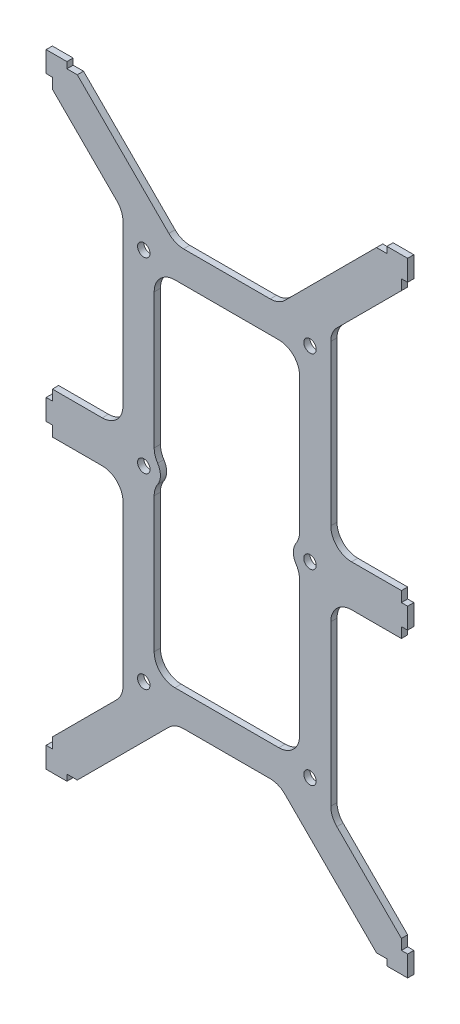
SolidWorks part; units mm, degrees
material "1023 Arkusz stali węglowej (SS)"
ref_plane "Płaszczyzna przednia" through (0, 0, 0) normal (0, 0, 1) x (1, 0, 0)
ref_plane "Płaszczyzna górna" through (0, 0, 0) normal (0, 1, 0) x (1, 0, 0)
ref_plane "Płaszczyzna prawa" through (0, 0, 0) normal (1, 0, 0) x (0, 0, -1)
sketch "Szkic1" plane through (0, 0, 0) normal (0, 0, 1) x (1, 0, 0)
  line L374 (-551.4403, 234.8816) -> (-551.4403, 224.8816)
  line L375 (-551.4403, 224.8816) -> (-548.4403, 224.8816)
  line L376 (-548.4403, 224.8816) -> (-548.4403, 219.8816)
  line L377 (-551.4403, 234.8816) -> (-541.4403, 234.8816)
  line L378 (-541.4403, 234.8816) -> (-541.4403, 231.8816)
  line L379 (-541.4403, 231.8816) -> (-536.4403, 231.8816)
  line L380 (-536.4403, 231.8816) -> (-492.3692, 187.8105)
  line L381 (-514.4403, 181.7395) -> (-514.4403, 104.8816)
  line L382 (-499.4403, 159.8816) -> (-499.4403, 94.8315)
  line L383 (-548.4403, 219.8816) -> (-517.3692, 188.8105)
  line L384 (-551.4403, 89.8816) -> (-548.4403, 89.8816)
  line L385 (-548.4403, 94.8816) -> (-548.4403, 89.8816)
  line L386 (-548.4403, 94.8816) -> (-524.4403, 94.8816)
  line L387 (-551.4403, 89.8816) -> (-551.4403, 84.8816)
  line L388 (-485.2981, 184.8816) -> (-464.4403, 184.8816)
  line L389 (-489.4403, 169.8816) -> (-464.4403, 169.8816)
  line L390 (-377.4403, 234.8816) -> (-377.4403, 224.8816)
  line L391 (-377.4403, 224.8816) -> (-380.4403, 224.8816)
  line L392 (-380.4403, 224.8816) -> (-380.4403, 219.8816)
  line L393 (-377.4403, 234.8816) -> (-387.4403, 234.8816)
  line L394 (-387.4403, 234.8816) -> (-387.4403, 231.8816)
  line L395 (-387.4403, 231.8816) -> (-392.4403, 231.8816)
  line L396 (-392.4403, 231.8816) -> (-436.5113, 187.8105)
  line L397 (-414.4403, 181.7395) -> (-414.4403, 104.8816)
  line L398 (-429.4403, 159.8816) -> (-429.4403, 94.8315)
  line L399 (-380.4403, 219.8816) -> (-411.5113, 188.8105)
  line L400 (-377.4403, 89.8816) -> (-380.4403, 89.8816)
  line L401 (-380.4403, 94.8816) -> (-380.4403, 89.8816)
  line L402 (-380.4403, 94.8816) -> (-404.4403, 94.8816)
  line L403 (-377.4403, 89.8816) -> (-377.4403, 84.8816)
  line L404 (-443.5824, 184.8816) -> (-464.4403, 184.8816)
  line L405 (-439.4403, 169.8816) -> (-464.4403, 169.8816)
  line L406 (-551.4403, -65.1184) -> (-551.4403, -55.1184)
  line L407 (-551.4403, -55.1184) -> (-548.4403, -55.1184)
  line L408 (-548.4403, -55.1184) -> (-548.4403, -50.1184)
  line L409 (-551.4403, -65.1184) -> (-541.4403, -65.1184)
  line L410 (-541.4403, -65.1184) -> (-541.4403, -62.1184)
  line L411 (-541.4403, -62.1184) -> (-536.4403, -62.1184)
  line L412 (-536.4403, -62.1184) -> (-492.3692, -18.0473)
  line L413 (-514.4403, -11.9763) -> (-514.4403, 64.8816)
  line L414 (-499.4403, 9.8816) -> (-499.4403, 74.9317)
  line L415 (-548.4403, -50.1184) -> (-517.3692, -19.0473)
  line L416 (-551.4403, 79.8816) -> (-548.4403, 79.8816)
  line L417 (-548.4403, 74.8816) -> (-548.4403, 79.8816)
  line L418 (-548.4403, 74.8816) -> (-524.4403, 74.8816)
  line L419 (-551.4403, 79.8816) -> (-551.4403, 84.8816)
  line L420 (-485.2981, -15.1184) -> (-464.4403, -15.1184)
  line L421 (-489.4403, -0.1184) -> (-464.4403, -0.1184)
  line L422 (-377.4403, -65.1184) -> (-377.4403, -55.1184)
  line L423 (-377.4403, -55.1184) -> (-380.4403, -55.1184)
  line L424 (-380.4403, -55.1184) -> (-380.4403, -50.1184)
  line L425 (-377.4403, -65.1184) -> (-387.4403, -65.1184)
  line L426 (-387.4403, -65.1184) -> (-387.4403, -62.1184)
  line L427 (-387.4403, -62.1184) -> (-392.4403, -62.1184)
  line L428 (-392.4403, -62.1184) -> (-436.5113, -18.0473)
  line L429 (-414.4403, -11.9763) -> (-414.4403, 64.8816)
  line L430 (-429.4403, 9.8816) -> (-429.4403, 74.9317)
  line L431 (-380.4403, -50.1184) -> (-411.5113, -19.0473)
  line L432 (-377.4403, 79.8816) -> (-380.4403, 79.8816)
  line L433 (-380.4403, 74.8816) -> (-380.4403, 79.8816)
  line L434 (-380.4403, 74.8816) -> (-404.4403, 74.8816)
  line L435 (-377.4403, 79.8816) -> (-377.4403, 84.8816)
  line L436 (-443.5824, -15.1184) -> (-464.4403, -15.1184)
  line L437 (-439.4403, -0.1184) -> (-464.4403, -0.1184)
  arc A162 (-514.4403, 181.7395) -> (-517.3692, 188.8105) centre (-524.4403, 181.7395) ccw
  arc A163 (-489.4403, 169.8816) -> (-499.4403, 159.8816) centre (-489.4403, 159.8816) ccw
  arc A164 (-492.3692, 187.8105) -> (-485.2981, 184.8816) centre (-485.2981, 194.8816) ccw
  arc A165 (-524.4403, 94.8816) -> (-514.4403, 104.8816) centre (-524.4403, 104.8816) ccw
  circle A166 centre (-504.4403, 174.8816) radius 3
  arc A167 (-496.4403, 84.8816) -> (-497.7736, 89.3038) centre (-504.4403, 84.8816) ccw
  arc A168 (-501.4403, 84.8816) -> (-507.4403, 84.8816) centre (-504.4403, 84.8816) ccw
  arc A169 (-499.4403, 94.8315) -> (-497.7736, 89.3038) centre (-489.4403, 94.8315) ccw
  arc A170 (-411.5113, 188.8105) -> (-414.4403, 181.7395) centre (-404.4403, 181.7395) ccw
  arc A171 (-429.4403, 159.8816) -> (-439.4403, 169.8816) centre (-439.4403, 159.8816) ccw
  arc A172 (-443.5824, 184.8816) -> (-436.5113, 187.8105) centre (-443.5824, 194.8816) ccw
  arc A173 (-414.4403, 104.8816) -> (-404.4403, 94.8816) centre (-404.4403, 104.8816) ccw
  circle A174 centre (-424.4403, 174.8816) radius 3
  arc A175 (-431.1069, 89.3038) -> (-432.4403, 84.8816) centre (-424.4403, 84.8816) ccw
  arc A176 (-421.4403, 84.8816) -> (-427.4403, 84.8816) centre (-424.4403, 84.8816) ccw
  arc A177 (-431.1069, 89.3038) -> (-429.4403, 94.8315) centre (-439.4403, 94.8315) ccw
  arc A178 (-517.3692, -19.0473) -> (-514.4403, -11.9763) centre (-524.4403, -11.9763) ccw
  arc A179 (-499.4403, 9.8816) -> (-489.4403, -0.1184) centre (-489.4403, 9.8816) ccw
  arc A180 (-485.2981, -15.1184) -> (-492.3692, -18.0473) centre (-485.2981, -25.1184) ccw
  arc A181 (-514.4403, 64.8816) -> (-524.4403, 74.8816) centre (-524.4403, 64.8816) ccw
  circle A182 centre (-504.4403, -5.1184) radius 3
  arc A183 (-497.7736, 80.4594) -> (-496.4403, 84.8816) centre (-504.4403, 84.8816) ccw
  arc A184 (-507.4403, 84.8816) -> (-501.4403, 84.8816) centre (-504.4403, 84.8816) ccw
  arc A185 (-497.7736, 80.4594) -> (-499.4403, 74.9317) centre (-489.4403, 74.9317) ccw
  arc A186 (-414.4403, -11.9763) -> (-411.5113, -19.0473) centre (-404.4403, -11.9763) ccw
  arc A187 (-439.4403, -0.1184) -> (-429.4403, 9.8816) centre (-439.4403, 9.8816) ccw
  arc A188 (-436.5113, -18.0473) -> (-443.5824, -15.1184) centre (-443.5824, -25.1184) ccw
  arc A189 (-404.4403, 74.8816) -> (-414.4403, 64.8816) centre (-404.4403, 64.8816) ccw
  circle A190 centre (-424.4403, -5.1184) radius 3
  arc A191 (-432.4403, 84.8816) -> (-431.1069, 80.4594) centre (-424.4403, 84.8816) ccw
  arc A192 (-427.4403, 84.8816) -> (-421.4403, 84.8816) centre (-424.4403, 84.8816) ccw
  arc A193 (-429.4403, 74.9317) -> (-431.1069, 80.4594) centre (-439.4403, 74.9317) ccw
extrude "Dodanie-wyciągnięcie1" add sketch "Szkic1" along normal blind 3
